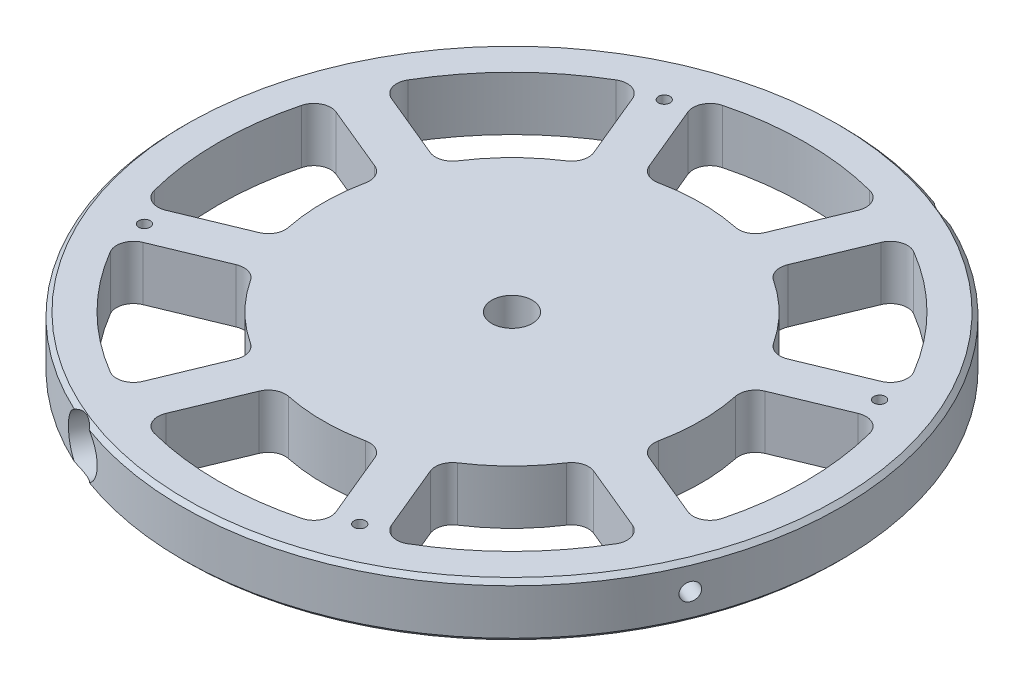
SolidWorks part; units mm, degrees
material "6061-T6 (SS)"
ref_plane "Front Plane" through (0, 0, 0) normal (0, 0, 1) x (1, 0, 0)
ref_plane "Top Plane" through (0, 0, 0) normal (0, 1, 0) x (1, 0, 0)
ref_plane "Right Plane" through (0, 0, 0) normal (1, 0, 0) x (0, 0, -1)
sketch "Sketch2" plane through (0, 0, 0) normal (1, 0, 0) x (0, 0, -1)
  line L0 (0, 0) -> (-77.55, 0)
  line L1 (-77.55, 0) -> (-77.55, 12.7)
  line L2 (-77.55, 12.7) -> (0, 12.7)
  line L5 (0, 12.7) -> (0, 0)
  dimension "D1" = 77.55
  dimension "D2" = 12.7
ref_axis "Axis1" through (0, -0.75, 0) along (0, 1, 0)
revolve "Revolve1" add sketch "Sketch2" angle 360 about axis through (0, -0.75, 0) along (0, 1, 0)
hole_wizard "#6-32 Tapped Hole2" positions "Sketch6" profile "Sketch7" tap size "#6-32" standard "ANSI Inch" end condition through all
sketch "Sketch6" plane through (0, 12.7, 0) normal (0, 1, 0) x (1, 0, 0)
  line L0 (0, 0) -> (-53.438, 129.0108) construction
  line L2 (0, 0) -> (0, 109.0908) construction
  point P0 (-25.3336, 61.1608)
  dimension "D1" = 22.5
  dimension "D2" = 66.2
sketch "Sketch7" plane through (-25.3336, 12.7, -61.1608) normal (1, 0, 0) x (0, 0, 1)
  line L0 (0, 0) -> (0, 12.7)
  line L1 (0, 12.7) -> (1.3525, 12.7)
  line L2 (1.3525, 12.7) -> (1.3525, 0)
  line L5 (1.3525, 0) -> (0, 0)
  line L11 (0, -6.35) -> (0, 107.95) construction
  dimension "Thread Major Dia." = 2.7051
  dimension "Thru Tap Drill Depth" = 12.7
pattern_circular "CirPattern3" count 4 over 360 about axis through (0, -0.75, 0) along (0, 1, 0) of "#6-32 Tapped Hole2"
sketch "Sketch8" plane through (0, 12.7, 0) normal (0, 1, 0) x (1, 0, 0)
  line L4 (0, 0) -> (0, 93.9995) construction
  line L5 (0, 0) -> (113.8372, 0) construction
  line L6 (-12.2829, 42.7192) -> (-21.7355, 65.5398)
  line L7 (12.2829, 42.7192) -> (21.7355, 65.5398)
  line L8 (0, 0) -> (-25.3336, 61.1608) construction
  arc A0 (-12.2829, 42.7192) -> (12.2829, 42.7192) centre (0, 0) cw
  arc A1 (-21.7355, 65.5398) -> (21.7355, 65.5398) centre (0, 0) cw
  circle A2 centre (0, 0) radius 77.55 construction
  dimension "D1" = 44.45
  dimension "D2" = 8.5
  dimension "D3" = 5
extrude "Cut-Extrude1" cut sketch "Sketch8" against normal through all
fillet "Fillet1" radius 4 4 edges at (12.2829, 6.35, -42.7192) (21.7355, 6.35, -65.5398) (-12.2829, 6.35, -42.7192) (-21.7355, 6.35, -65.5398)
pattern_circular "CirPattern4" count 8 over 360 about axis through (0, -0.75, 0) along (0, 1, 0) of "Cut-Extrude1", "Fillet1"
chamfer "Chamfer1" distance 1 angle 45 2 edges at (0, 0, -77.55) (0, 12.7, -77.55)
ref_plane "Plane1" through (0, 0, 0) normal (0.9239, 0, 0.3827) x (0, 1, 0)
hole_wizard "#20 (0.161) Diameter Hole1" positions "Sketch16" profile "Sketch15" hole size "#20" standard "ANSI Inch" end condition through all
sketch "Sketch16" plane through (0, 0, 0) normal (0.9239, 0, 0.3827) x (0, 1, 0)
  point P0 (6.35, 0)
  dimension "D1" = 6.35
sketch "Sketch15" plane through (0, 6.35, 0) normal (0, 1, 0) x (-0.3827, 0, 0.9239)
  line L0 (0, 0) -> (0, 101.324)
  line L1 (0, 101.324) -> (2.0447, 101.324)
  line L2 (2.0447, 101.324) -> (2.0447, 0)
  line L5 (2.0447, 0) -> (0, 0)
  line L11 (0, -6.35) -> (0, 107.95) construction
  dimension "Thru Hole Dia." = 4.0894
  dimension "Thru Hole Depth" = 101.324
ref_plane "Plane2" through (29.6771, 0, -71.6469) normal (0.3827, 0, -0.9239) x (-0.9239, 0, -0.3827)
sketch "Sketch19" plane through (29.6771, 0, -71.6469) normal (0.3827, 0, -0.9239) x (-0.9239, 0, -0.3827)
  line L0 (-76.55, 0) -> (76.55, 0) construction
  line L2 (0, -0.75) -> (0, 15.75) construction
  circle A0 centre (0, 6.35) radius 5.5625 construction
  circle A1 centre (0, 6.35) radius 6.25
  dimension "D1" = 12.5
  dimension "D2" = 6.35
extrude "Cut-Extrude3" cut sketch "Sketch19" against normal blind 5
pattern_circular "CirPattern5" count 2 over 360 about axis through (0, -0.75, 0) along (0, 1, 0) of "Cut-Extrude3"
hole_wizard "#10-24 Tapped Hole1" positions "Sketch20" profile "Sketch21" tap size "#10-24" standard "ANSI Inch"
sketch "Sketch20" plane through (-27.7637, 0, 67.0275) normal (-0.3827, 0, 0.9239) x (0.9239, 0, 0.3827)
  circle A0 centre (0, 6.35) radius 6.25
  circle A1 centre (0, 6.35) radius 6.25 construction
  point P0 (0, 6.35)
sketch "Sketch21" plane through (-27.7637, 6.35, 67.0275) normal (0, 1, 0) x (0.9239, 0, 0.3827)
  line L0 (0, 0) -> (0, 51.9408)
  line L1 (0, 51.9408) -> (1.8986, 50.8)
  line L2 (1.8986, 50.8) -> (1.8986, 0)
  line L5 (1.8986, 0) -> (0, 0)
  line L10 (0, 51.9408) -> (-1.8986, 50.8) construction
  line L11 (0, -6.35) -> (0, 107.95) construction
  dimension "Tap Drill Dia." = 3.7973
  dimension "Tap Drill Depth" = 50.8
  dimension "Drill Angle" = 118
pattern_circular "CirPattern6" count 2 over 360 about axis through (0, -0.75, 0) along (0, 1, 0) of "#10-24 Tapped Hole1"
sketch "Sketch22" plane through (0, 12.7, 0) normal (0, 1, 0) x (1, 0, 0)
  circle A0 centre (0, 0) radius 4.765
  dimension "D1" = 9.53
extrude "Cut-Extrude4" cut sketch "Sketch22" against normal blind 12.8
equation "\"TubeDiameter\" = 6.500in"
equation "\"D1@Sketch2\"=(\"TubeDiameter\"/2)-5mm"
equation "\"D2@Sketch6\"=66.2"
